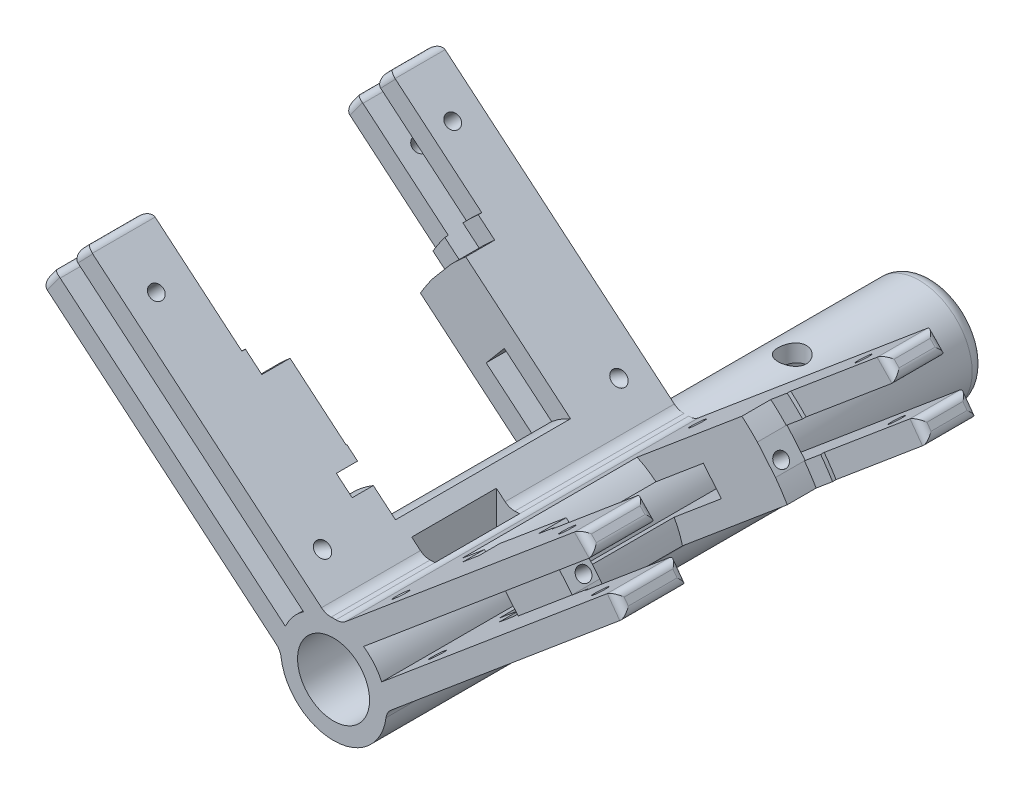
SolidWorks part; units mm, degrees
material "尼龙 101"
ref_plane "前视基准面" through (0, 0, 0) normal (0, 0, 1) x (1, 0, 0)
ref_plane "上视基准面" through (0, 0, 0) normal (0, 1, 0) x (1, 0, 0)
ref_plane "右视基准面" through (0, 0, 0) normal (1, 0, 0) x (0, 0, -1)
other "Configuration Table"
sketch "草图1" plane through (0, 0, 0) normal (0, 0, 1) x (1, 0, 0)
  circle A0 centre (0, 0) radius 5.1
  circle A1 centre (0, 0) radius 7.5
  dimension "D1" = 10.2
  dimension "D2" = 15
extrude "凸台-拉伸1" add sketch "草图1" along normal blind 35
sketch "草图2" plane through (0, 0, 35) normal (0, 0, 1) x (1, 0, 0)
  line L0 (0, -50) -> (0, 50) construction
  line L6 (-38.3022, -32.1394) -> (38.3022, 32.1394) construction
  line L7 (36.986, 33.6457) -> (4.2517, 6.1784)
  line L8 (1.0684, 7.4235) -> (34.8963, 35.8085)
  line L9 (34.8963, 35.8085) -> (36.986, 33.6457)
  line L10 (41.3242, 28.1481) -> (39.5571, 30.5816)
  line L11 (39.5571, 30.5816) -> (6.8229, 3.1142)
  line L12 (7.4963, -0.2369) -> (41.3242, 28.1481)
  line L13 (-41.3242, 28.1481) -> (-39.5571, 30.5816)
  line L14 (-34.8963, 35.8085) -> (-36.986, 33.6457)
  line L15 (-7.4963, -0.2369) -> (-41.3242, 28.1481)
  line L16 (-39.5571, 30.5816) -> (-6.8229, 3.1142)
  line L17 (-36.986, 33.6457) -> (-4.2517, 6.1784)
  line L18 (-1.0684, 7.4235) -> (-34.8963, 35.8085)
  circle A0 centre (0, 0) radius 50 construction
  circle A1 centre (0, 0) radius 5.1
  circle A2 centre (0, 0) radius 7.5 construction
  circle M16 centre (0, 0) radius 7.5
  circle M17 centre (0, 0) radius 5.1
  dimension "60" = 100
  dimension "D6" = 10.2
  dimension "D1" = 50
  dimension "D4" = 2
  dimension "D5" = 3
extrude "凸台-拉伸2" add sketch "草图2" along normal blind 50 contours M16 M17 | L12 L10 L11 M16 | L9 L8 L7 M16 | L18 L14 L17 M16 | L16 L13 L15 M16 region at (19.351, 20.8169, 35) region at (5.5828, 4.6846, 35) region at (23.861, 15.4422, 35) region at (-19.351, 20.8169, 35) region at (-23.861, 15.4422, 35)
fillet "圆角2" radius 2 4 edges at (7.4963, -0.2369, 60) (1.0684, 7.4235, 60) (-1.0684, 7.4235, 60) (-7.4963, -0.2369, 60)
fillet "圆角3" radius 2 1 edges at (7.5, 0, 0)
sketch "草图3" plane through (0, 0, 0) normal (0, 1, 0) x (1, 0, 0)
  line L0 (0.332, -85) -> (0.332, -35) construction
  line L1 (-2.9417, -58.9811) -> (0.332, -58.9811)
  line L2 (-2.9417, -58.9811) -> (-2.9417, -70.9811)
  line L3 (-2.9417, -70.9811) -> (0.332, -70.9811)
  line L4 (0.332, -58.9811) -> (0.332, -70.9811)
  line L5 (-2.9417, -58.9811) -> (0.332, -70.9811) construction
  line L6 (-2.9417, -70.9811) -> (0.332, -58.9811) construction
  circle A0 centre (0, -20) radius 2
  point P4 (-1.3049, -64.9811)
  dimension "D2" = 4
  dimension "D1" = 20
  dimension "D3" = 3.2737
  dimension "D4" = 12
  dimension "D5" = 45
extrude "切除-拉伸2" cut sketch "草图3" along normal through all
ref_plane "基准面2" through (0, 0, 0) normal (-0.6428, 0.766, 0) x (0.766, 0.6428, 0)
sketch "草图12" plane through (0, 0, 0) normal (-0.6428, 0.766, 0) x (0.766, 0.6428, 0)
  line L0 (7.5, -85) -> (7.5, -2) construction
  line L5 (12.497, -39) -> (42.497, -39) construction
  line L6 (6.4226, -35) -> (49.7494, -35) construction
  line L7 (12.497, -39) -> (12.497, -81) construction
  line L12 (6.4226, -85) -> (49.7494, -85) construction
  line L19 (29.65, -42.1) -> (50, -42.1)
  line L35 (11, -46.2) -> (29.65, -46.2)
  line L36 (29.65, -42.1) -> (29.65, -46.2)
  line L37 (33.15, -42.1) -> (29.65, -42.1)
  line L38 (33.15, -42.1) -> (33.15, -46.2)
  line L39 (33.15, -46.2) -> (34.65, -46.2)
  line L40 (34.65, -46.2) -> (34.65, -54.5)
  line L41 (34.65, -54.5) -> (38.45, -54.5)
  line L42 (38.45, -60.9725) -> (38.45, -54.5)
  line L43 (38.45, -60.9725) -> (43.45, -60.9725)
  line L45 (38.45, -67.7275) -> (43.45, -67.7275)
  line L46 (38.45, -72) -> (38.45, -67.7275)
  line L47 (33.15, -72) -> (38.45, -72)
  line L48 (33.15, -76.1) -> (33.15, -72)
  line L49 (29.65, -76.1) -> (33.15, -76.1)
  line L50 (29.65, -76.1) -> (29.65, -72)
  line L51 (11, -72) -> (29.65, -72)
  line L52 (11, -46.2) -> (11, -72)
  line L53 (0, 0) -> (0, -20) construction
  line L54 (11.5, -46.7) -> (30.15, -46.7)
  line L55 (30.15, -42.6) -> (30.15, -46.7)
  line L56 (32.65, -42.6) -> (30.15, -42.6)
  line L57 (32.65, -42.6) -> (32.65, -46.7)
  line L58 (32.65, -46.7) -> (34.15, -46.7)
  line L59 (34.15, -46.7) -> (34.15, -55)
  line L60 (34.15, -55) -> (37.95, -55)
  line L61 (37.95, -61.4725) -> (37.95, -55)
  line L62 (37.95, -61.4725) -> (42.95, -61.4725)
  line L63 (42.95, -61.4725) -> (42.95, -67.2275)
  line L64 (37.95, -67.2275) -> (42.95, -67.2275)
  line L65 (37.95, -71.5) -> (37.95, -67.2275)
  line L66 (32.65, -71.5) -> (37.95, -71.5)
  line L67 (32.65, -75.6) -> (32.65, -71.5)
  line L68 (30.15, -75.6) -> (32.65, -75.6)
  line L69 (30.15, -75.6) -> (30.15, -71.5)
  line L70 (11.5, -71.5) -> (30.15, -71.5)
  line L71 (11.5, -46.7) -> (11.5, -71.5)
  line L72 (43.45, -60.9725) -> (43.45, -67.7275) construction
  line L73 (43.45, -60.9725) -> (43.45, -67.7275)
  line L75 (50, -42.1) -> (50, -76.1)
  line L76 (50, -76.1) -> (29.65, -76.1)
  line L78 (32.65, -42.6) -> (33.15, -42.6)
  line L79 (32.65, -75.6) -> (33.15, -75.6)
  circle A8 centre (12.497, -39) radius 1
  circle A9 centre (42.497, -39) radius 1
  circle A10 centre (42.497, -81) radius 1
  circle A11 centre (12.497, -81) radius 1
  dimension "D6" = 4.997
  dimension "D4" = 2
  dimension "D2" = 20
  dimension "D3" = 5
  dimension "D5" = 4
  dimension "D8" = 30
  dimension "D9" = 4
  dimension "D10" = 2
  dimension "D7" = 90
  dimension "D1" = 0.5
  dimension "D11" = 2
revolve "切除-旋转3" cut sketch "草图12" angle 360 about L53
ref_plane "基准面3" through (0, 0, 75.5) normal (0, 0, 1) x (1, 0, 0)
sketch "草图16" plane through (0, 0, 75.5) normal (0, 0, 1) x (1, 0, 0)
  line L0 (14.0993, 14.4416) -> (21.7598, 20.8694)
  line L3 (21.7598, 20.8694) -> (24.3309, 17.8053)
  line L5 (24.3309, 17.8053) -> (16.6705, 11.3774)
  line L6 (0, 0) -> (0, 4.0927) construction
  line L7 (-14.0993, 14.4416) -> (-16.6705, 11.3774)
  line L8 (-24.3309, 17.8053) -> (-16.6705, 11.3774)
  line L9 (-21.7598, 20.8694) -> (-24.3309, 17.8053)
  line L10 (36.986, 33.6457) -> (4.2517, 6.1784) construction
  line L11 (39.5571, 30.5816) -> (6.8229, 3.1142) construction
  line L12 (14.0993, 14.4416) -> (16.6705, 11.3774)
  line L13 (-14.0993, 14.4416) -> (-21.7598, 20.8694)
  arc A1 (25.9904, 15.2815) -> (24.3309, 17.8053) centre (0, 0) ccw construction
  dimension "D1" = 10
extrude "凸台-拉伸3" add sketch "草图16" against normal blind 33 contours L5 L3 L0 | L7 L13 L9 L8 region at (19.2151, 16.1234, 75.5) region at (-19.2151, 16.1234, 75.5)
sketch "草图20" plane through (23.0454, 19.3374, 0) normal (0.766, 0.6428, 0) x (0, 0, -1)
  circle A0 centre (-73.1, -0.75) radius 1
  circle A1 centre (-45.1, -0.75) radius 1
  dimension "D1" = 2
  dimension "D2" = 2
extrude "切除-拉伸3" cut sketch "草图20" against normal blind 5
sketch "草图21" plane through (-23.0454, 19.3374, 0) normal (-0.766, 0.6428, 0) x (0, 0, 1)
  circle A0 centre (73.1, -0.75) radius 1
  circle A1 centre (45.1, -0.75) radius 1
  dimension "D1" = 2
  dimension "D2" = 2
extrude "切除-拉伸4" cut sketch "草图21" against normal blind 5
fillet "圆角5" radius 1 32 edges at (-40.4407, 29.3648, 76.1) (-39.5571, 30.5816, 80.55) (-41.3242, 28.1481, 80.55) (-35.9411, 34.7271, 76.1) (-34.8963, 35.8085, 80.55) (-36.986, 33.6457, 80.55) (-41.3242, 28.1481, 38.55) (-40.4407, 29.3648, 35) (-39.5571, 30.5816, 38.55) (-40.4407, 29.3648, 42.1) (-35.9411, 34.7271, 35) (-34.8963, 35.8085, 38.55) (-35.9411, 34.7271, 42.1) (-36.986, 33.6457, 38.55) (35.9411, 34.7271, 76.1) (36.986, 33.6457, 80.55) (34.8963, 35.8085, 80.55) (40.4407, 29.3648, 76.1) (41.3242, 28.1481, 80.55) (39.5571, 30.5816, 80.55) (40.4407, 29.3648, 35) (41.3242, 28.1481, 38.55) (40.4407, 29.3648, 42.1) (39.5571, 30.5816, 38.55) (34.8963, 35.8085, 38.55) (35.9411, 34.7271, 35) (36.986, 33.6457, 38.55) (35.9411, 34.7271, 42.1) (35.9411, 34.7271, 85) (-40.4407, 29.3648, 85) (-35.9411, 34.7271, 85) (40.4407, 29.3648, 85)
sketch "草图22" plane through (0, 0, 0) normal (-0.6428, 0.766, 0) x (0.766, 0.6428, 0)
  line L0 (29.7325, -71.5) -> (10.3562, -71.5) construction
  line L1 (30.1836, -46.7) -> (19.9836, -46.7)
  line L2 (30.1836, -46.7) -> (30.1836, -71.6)
  line L3 (30.1836, -71.6) -> (19.9836, -71.6)
  line L4 (19.9836, -46.7) -> (19.9836, -71.6)
  line L5 (30.0836, -46.7) -> (20.0836, -46.7) construction
  line L10 (20.0836, -46.7) -> (20.0836, -71.5) construction
  line L11 (0, 0) -> (0, -23.6618) construction
  line L12 (5.5, 0) -> (-5.5, 0) construction
  line L13 (20.0836, -71.5) -> (20.0836, -75.5) construction
  line L14 (18.0836, -71.5) -> (15.2973, -71.5)
  line L15 (18.0836, -71.5) -> (18.0836, -74.5)
  line L16 (18.0836, -74.5) -> (15.2973, -74.5)
  line L17 (15.2973, -71.5) -> (15.2973, -74.5)
  point P14 (20.0443, -46.7)
  point P15 (0, 0)
  point P20 (0, 0)
  point P21 (0, 0)
  point P22 (0, 0)
  point P23 (0, 0)
  dimension "D1" = 3
  dimension "D2" = 2.7863
  dimension "D3" = 2
  dimension "D4" = 10.2
  dimension "D5" = 24.9
  dimension "D6" = 0.1
revolve "切除-旋转5" cut sketch "草图22" angle 360 about L11
